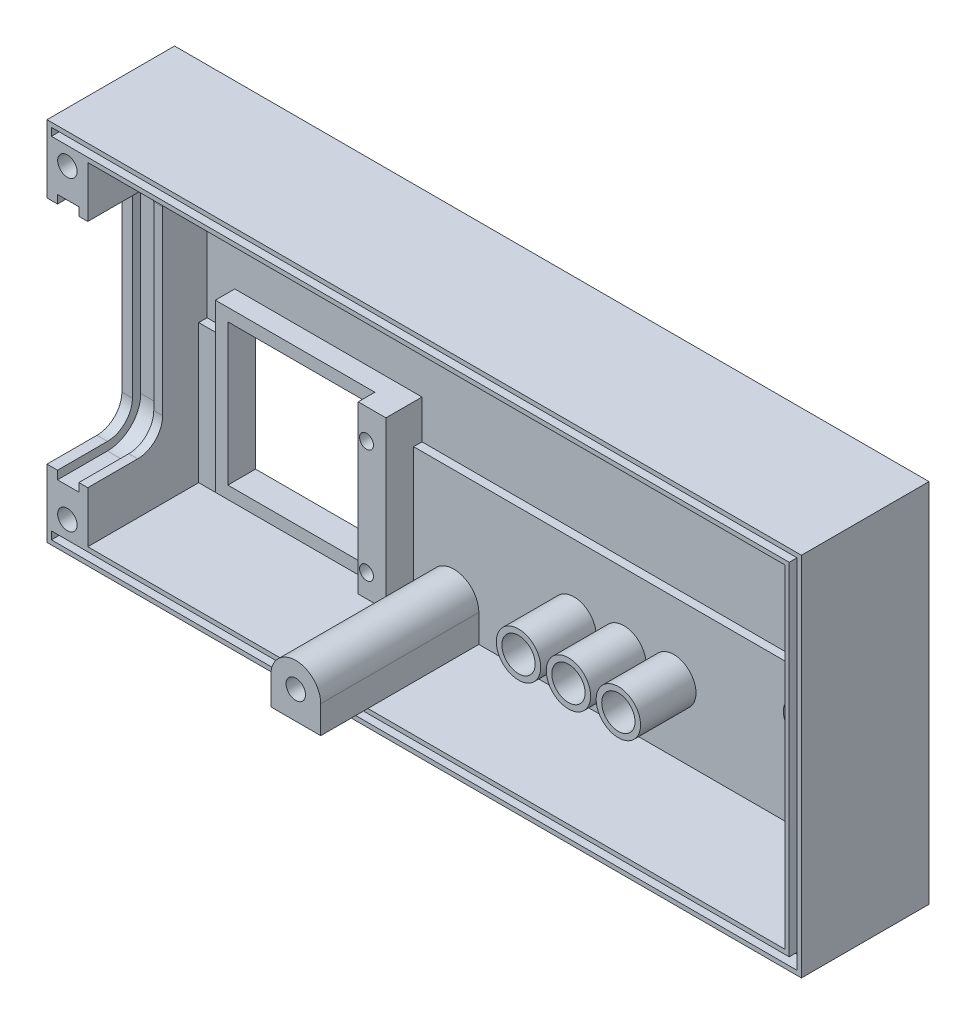
SolidWorks part; units mm, degrees
ref_plane "Płaszczyzna przednia" through (0, 0, 0) normal (0, 0, 1) x (1, 0, 0)
ref_plane "Płaszczyzna górna" through (0, 0, 0) normal (0, 1, 0) x (1, 0, 0)
ref_plane "Płaszczyzna prawa" through (0, 0, 0) normal (1, 0, 0) x (0, 0, -1)
sketch "Szkic1" plane through (0, 0, 0) normal (0, 0, 1) x (1, 0, 0)
  line L1 (65, -30) -> (-65, -30)
  line L2 (65, -30) -> (65, 30)
  line L3 (65, 30) -> (-65, 30)
  line L4 (-65, -30) -> (-65, 30)
  line L5 (65, -30) -> (-65, 30) construction
  line L6 (65, 30) -> (-65, -30) construction
  point P0 (0, 0)
  dimension "D1" = 130
  dimension "D2" = 60
extrude "Dodanie-wyciągnięcie1" add sketch "Szkic1" along normal blind 20
shell "Skorupa1" thickness 3 removed face at (0, 0, 20) outward yes
sketch "Szkic4" plane through (-65, 0, 0) normal (1, 0, 0) x (0, 0, -1)
  line L4 (0, -30) -> (0, 30)
  line L5 (0, 30) -> (-20, 30)
  line L6 (-20, 30) -> (-20, -30)
  line L7 (-20, -30) -> (0, -30)
  line L8 (0, -30) -> (0, 30)
  line L9 (0, 30) -> (-20, 30)
  line L10 (-20, 30) -> (-20, -30)
  line L11 (-20, -30) -> (0, -30)
  dimension "D1" = 0
extrude "Wytnij-wyciągnięcie1" cut sketch "Szkic4" against normal blind 1.1
sketch "Szkic5" plane through (-66.1, 0, 0) normal (1, 0, 0) x (0, 0, -1)
  line L0 (-20, 30) -> (-20, -30) construction
  line L1 (-20, 22.275) -> (-11, 22.275)
  line L2 (-26, 16.275) -> (-26, -16.275)
  line L3 (-20, -22.275) -> (-11, -22.275)
  line L4 (-5, 16.275) -> (-5, -16.275)
  line L9 (-20, -30) -> (0, -30)
  line L10 (0, -30) -> (0, 30)
  line L11 (0, 30) -> (-20, 30)
  line L12 (-20, 30) -> (-20, -30)
  line L13 (-20, -30) -> (0, -30)
  line L14 (0, -30) -> (0, 30)
  line L15 (0, 30) -> (-20, 30)
  line L16 (-20, 30) -> (-20, -30)
  arc A0 (-5, -16.275) -> (-11, -22.275) centre (-11, -16.275) cw
  arc A1 (-5, 16.275) -> (-11, 22.275) centre (-11, 16.275) ccw
  arc A2 (-20, -22.275) -> (-26, -16.275) centre (-20, -16.275) cw
  arc A3 (-26, 16.275) -> (-20, 22.275) centre (-20, 16.275) cw
  point P8 (-5, 0)
  point P17 (-20, 22.175)
  point P19 (0, 0)
  line M5 (-20, -30) -> (0, -30)
  line M6 (0, -30) -> (0, 30)
  line M7 (0, 30) -> (-20, 30)
  line M8 (-20, 30) -> (-20, -30)
  dimension "D3" = 6
  dimension "D4" = 6
  dimension "D5" = 6
  dimension "D6" = 6
  dimension "D1" = 32.55
  dimension "D2" = 0
  dimension "D7" = 21
extrude "Dodanie-wyciągnięcie2" add sketch "Szkic5" along normal blind 3.85 contours A1 L4 A0 L3 L1 M8 M5 M6 M7 region at (-66.1, 26.1375, 19.3675)
sketch "Szkic7" plane through (-62.25, 0, 0) normal (1, 0, 0) x (0, 0, -1)
  line L0 (-20, 20.775) -> (-11, 20.775)
  line L1 (-6.5, 16.275) -> (-6.5, -16.275)
  line L2 (-11, -20.775) -> (-20, -20.775)
  line L3 (-20, 22.275) -> (-20, 20.775)
  line L4 (-20, -20.775) -> (-20, -22.275)
  line L8 (-5, 16.275) -> (-5, -16.275)
  line L9 (-11, -22.275) -> (-20, -22.275)
  line L15 (-20, -22.275) -> (-20, -30)
  line L24 (-20, -30) -> (0, -30)
  line L25 (0, -30) -> (0, 30)
  line L26 (0, 30) -> (-20, 30)
  line L27 (-20, 30) -> (-20, 22.275)
  line L28 (-20, 22.275) -> (-11, 22.275)
  line L29 (-5, 16.275) -> (-5, -16.275)
  line L30 (-11, -22.275) -> (-20, -22.275)
  line L31 (-20, -22.275) -> (-20, -30)
  line L32 (-20, -30) -> (0, -30)
  line L33 (0, -30) -> (0, 30)
  line L34 (0, 30) -> (-20, 30)
  line L35 (-20, 30) -> (-20, 22.275)
  line L36 (-20, 22.275) -> (-11, 22.275)
  arc A0 (-6.5, 16.275) -> (-11, 20.775) centre (-11, 16.275) ccw
  arc A1 (-11, -20.775) -> (-6.5, -16.275) centre (-11, -16.275) ccw
  arc A6 (-5, 16.275) -> (-11, 22.275) centre (-11, 16.275) ccw
  arc A7 (-11, -22.275) -> (-5, -16.275) centre (-11, -16.275) ccw
  arc A8 (-5, 16.275) -> (-11, 22.275) centre (-11, 16.275) ccw
  arc A9 (-11, -22.275) -> (-5, -16.275) centre (-11, -16.275) ccw
  arc M11 (-11, 22.275) -> (-5, 16.275) centre (-11, 16.275) cw
  line M12 (-5, 16.275) -> (-5, -16.275)
  arc M13 (-5, -16.275) -> (-11, -22.275) centre (-11, -16.275) cw
  line M14 (-11, -22.275) -> (-20, -22.275)
  line M15 (-20, -22.275) -> (-20, -30)
  line M16 (-20, -30) -> (0, -30)
  line M17 (0, -30) -> (0, 30)
  line M18 (0, 30) -> (-20, 30)
  line M19 (-20, 30) -> (-20, 22.275)
  line M20 (-20, 22.275) -> (-11, 22.275)
  dimension "D1" = 0
  dimension "D2" = 1.5
extrude "Dodanie-wyciągnięcie3" add sketch "Szkic7" along normal blind 1.6 contours M20 M11 M12 M13 M14 M15 M16 M17 M18 M19 | M20 M14 M13 M12 M11 region at (-62.25, 21.525, 19.5299) region at (-62.25, 26.1375, 19.3675)
sketch "Szkic8" plane through (-66.1, 0, 0) normal (1, 0, 0) x (0, 0, -1)
  line L0 (-11, -20.775) -> (-20, -20.775) construction
  line L1 (-6.5, 16.275) -> (-6.5, -16.275) construction
  line L2 (-20, 20.775) -> (-11, 20.775) construction
  line L3 (-11, -20.775) -> (-20, -20.775)
  line L4 (-6.5, 16.275) -> (-6.5, -16.275)
  line L5 (-20, 20.775) -> (-11, 20.775)
  line L9 (-20, 20.775) -> (-20, -20.775)
  line L11 (-20, 20.975) -> (-11, 20.975)
  line L12 (-6.3, 16.275) -> (-6.3, -16.275)
  line L13 (-11, -20.975) -> (-20, -20.975)
  line L14 (-20, 20.775) -> (-20, 20.975)
  line L15 (-20, -20.775) -> (-20, -20.975)
  arc A0 (-11, -20.775) -> (-6.5, -16.275) centre (-11, -16.275) ccw construction
  arc A1 (-6.5, 16.275) -> (-11, 20.775) centre (-11, 16.275) ccw construction
  arc A2 (-11, -20.775) -> (-6.5, -16.275) centre (-11, -16.275) ccw
  arc A3 (-6.5, 16.275) -> (-11, 20.775) centre (-11, 16.275) ccw
  arc A6 (-6.3, 16.275) -> (-11, 20.975) centre (-11, 16.275) ccw
  arc A7 (-11, -20.975) -> (-6.3, -16.275) centre (-11, -16.275) ccw
  line M10 (-20, 22.275) -> (-20, -22.275)
  dimension "D2" = 0.2
  dimension "D1" = 41.55
  dimension "D3" = 41.95
extrude "Wytnij-wyciągnięcie2" cut sketch "Szkic8" against normal through all contours M10 region at (-66.1, 0, 13.3404)
sketch "Szkic9" plane through (0, 0, 20) normal (0, 0, 1) x (1, 0, 0)
  line L0 (-68, 33) -> (-68, 20.775) construction
  line L1 (68, 33) -> (-68, 33) construction
  line L4 (-19.15, -25) -> (-19.15, -30)
  line L9 (-60.65, -30) -> (65, -30) construction
  line L10 (-19.15, -30) -> (-10.15, -30)
  line L11 (-10.15, -30) -> (-10.15, -25) construction
  line L12 (-10.15, -30) -> (-10.15, -25)
  line L13 (-60.65, -20.775) -> (-60.65, -30) construction
  circle A2 centre (-64.325, 27.5875) radius 1.75
  circle A3 centre (-64.325, -27.5875) radius 1.75
  circle A4 centre (-14.65, -25) radius 1.75
  arc A5 (-10.15, -25) -> (-19.15, -25) centre (-14.65, -25) ccw
  point P0 (-64.325, 27.5875)
  point P3 (-64.325, -27.5875)
  line M16 (-60.65, 30) -> (65, 30)
  line M18 (65, -30) -> (-60.65, -30)
  dimension "D8" = 3.5
  dimension "D9" = 3.5
  dimension "D11" = 3.5
  dimension "D12" = 4.5
  dimension "D1" = 3.675
  dimension "D2" = 5.4125
  dimension "D10" = 46
  dimension "D13" = 5
  dimension "D3" = 2
extrude "Dodanie-wyciągnięcie4" add sketch "Szkic9" along direction (0, 0, 1) on the side against the normal up to surface (20 mm away) and the other way blind 8.5 contours M16 | L12 A5 L4 A4 M18 region at (-14.65, -20.6309, 20) up to face at (2.175, 0, 0)
extrude "Wytnij-wyciągnięcie3" cut sketch "Szkic9<3>" against normal through all contours A2 | A3 | A4 region at (-64.325, 27.5875, 20)
sketch "Szkic9<3>" plane through (0, 0, 20) normal (0, 0, 1) x (1, 0, 0) same geometry as "Szkic9"
sketch "Szkic10" plane through (0, 0, -3) normal (0, 0, -1) x (-1, 0, 0)
  circle A1 centre (64.325, 27.5875) radius 3
  circle A2 centre (64.325, -27.5875) radius 3
  circle A3 centre (14.65, -25) radius 3
  circle M11 centre (14.65, -25) radius 1.75
  dimension "D1" = 6
  dimension "D2" = 6
  dimension "D3" = 6
extrude "Wytnij-wyciągnięcie4" cut sketch "Szkic10" against normal offset from surface (11 mm away) 12 contours A2 | A1 up to face at (-62.575, 27.5875, 20)
sketch "Szkic11" plane through (0, 0, 20) normal (0, 0, 1) x (1, 0, 0)
  line L22 (-10.15, -30.8) -> (-19.15, -30.8)
  line L23 (-19.15, -30.8) -> (-10.15, -30.8)
  line L24 (-61.45, -30.8) -> (-67.2, -30.8)
  line L25 (-61.45, 30.8) -> (-67.2, 30.8)
  line L26 (-67.2, 30.8) -> (-67.2, 32.2)
  line L27 (-67.2, -32.2) -> (-67.2, -30.8)
  line L28 (-10.15, -30.8) -> (-19.15, -30.8)
  line L29 (-66.9, -23.075) -> (-66.9, -21.575)
  line L31 (-66.9, -21.575) -> (-67.2, -21.575)
  line L32 (-66.9, -21.575) -> (-67.2, -21.575)
  line L33 (-67.2, 21.575) -> (-66.9, 21.575)
  line L34 (-67.2, 21.575) -> (-66.9, 21.575)
  line L35 (-66.9, 21.575) -> (-66.9, 23.075)
  line L46 (-67.2, -21.575) -> (-67.2, -32.2)
  line L47 (-67.2, -32.2) -> (67.2, -32.2)
  line L48 (67.2, -32.2) -> (67.2, 32.2)
  line L49 (67.2, 32.2) -> (-67.2, 32.2)
  line L50 (-67.2, 32.2) -> (-67.2, 21.575)
  line L51 (-66.9, 23.075) -> (-61.45, 23.075)
  line L52 (-61.45, 23.075) -> (-61.45, 30.8)
  line L53 (-61.45, 30.8) -> (65.8, 30.8)
  line L54 (65.8, 30.8) -> (65.8, -30.8)
  line L55 (65.8, -30.8) -> (-10.15, -30.8)
  line L58 (-19.15, -30.8) -> (-61.45, -30.8)
  line L59 (-61.45, -30.8) -> (-61.45, -23.075)
  line L60 (-61.45, -23.075) -> (-66.9, -23.075)
  line L62 (-67.2, -32.2) -> (67.2, -32.2)
  line L63 (67.2, -32.2) -> (67.2, 32.2)
  line L64 (67.2, 32.2) -> (-67.2, 32.2)
  line L68 (-61.45, 30.8) -> (65.8, 30.8)
  line L69 (65.8, 30.8) -> (65.8, -30.8)
  line L70 (65.8, -30.8) -> (-10.15, -30.8)
  line L73 (-19.15, -30.8) -> (-61.45, -30.8)
  dimension "D1" = 0.8
extrude "Wytnij-wyciągnięcie5" cut sketch "Szkic11" against normal blind 2.5 contours L23 L73 L24 L27 L62 L63 L64 L26 L25 L68 L69 L70 region at (27.825, -30.949, 20)
sketch "Szkic12" plane through (0, 0, -3) normal (0, 0, -1) x (-1, 0, 0)
  line L0 (-25, 33) -> (-25, -18) construction
  line L1 (-68, -33) -> (-48, -33) construction
  line L2 (-68, -33) -> (-68, -13) construction
  line L3 (-68, -13) -> (-48, -13) construction
  line L4 (-48, -33) -> (-48, -13) construction
  line L5 (-68, 33) -> (68, 33) construction
  line L6 (-25, -18) -> (-68, -18) construction
  circle A0 centre (-48, -13) radius 3.25
  circle A1 centre (-25, -18) radius 3
  circle A2 centre (-16, -18) radius 3
  circle A3 centre (-7, -18) radius 3
  dimension "D1" = 6.5
  dimension "D6" = 6
  dimension "D2" = 20
  dimension "D3" = 20
  dimension "D4" = 51
  dimension "D5" = 43
  dimension "D7" = 3
extrude "Wytnij-wyciągnięcie6" cut sketch "Szkic12" against normal up to next
extrude "Wytnij-wyciągnięcie7" cut sketch "Szkic10<4>" against normal offset from surface (19.5 mm away) 12 contours A3 M11 region at (-11.7349, -25, -3) up to face at (-12.9, -25, 28.5)
sketch "Szkic10<4>" plane through (0, 0, -3) normal (0, 0, -1) x (-1, 0, 0) same geometry as "Szkic10"
sketch "Szkic13" plane through (0, 0, 0) normal (0, 0, 1) x (1, 0, 0)
  circle A0 centre (7, -18) radius 3 construction
  circle A1 centre (16, -18) radius 3 construction
  circle A2 centre (25, -18) radius 3 construction
  circle A3 centre (7, -18) radius 3
  circle A4 centre (16, -18) radius 3
  circle A5 centre (25, -18) radius 3
  circle A6 centre (7, -18) radius 4
  circle A7 centre (16, -18) radius 4
  circle A8 centre (25, -18) radius 4
  dimension "D1" = 8
  dimension "D2" = 8
  dimension "D3" = 8
extrude "Dodanie-wyciągnięcie5" add sketch "Szkic13" along normal blind 10
sketch "Szkic14" plane through (0, 0, 0) normal (0, 0, 1) x (1, 0, 0)
  line L0 (65, -30) -> (65, 30) construction
  line L1 (65, -5) -> (-60.65, -5)
  line L2 (65, -5) -> (65, 30)
  line L3 (65, 30) -> (-60.65, 30)
  line L6 (-60.65, -30) -> (-60.65, 30) construction
  line L7 (-60.65, -30) -> (-60.65, 30)
  point P8 (0, 0)
  point P11 (-60.65, -4.997)
  point P12 (0, 0)
  point P13 (-60.6941, 30)
  line M7 (65, -30) -> (65, 30)
  line M8 (65, 30) -> (-60.65, 30)
  line M9 (-60.65, 30) -> (-60.65, -30)
  dimension "D2" = 35
extrude "Wytnij-wyciągnięcie8" cut sketch "Szkic14" against normal blind 1.5 contours L1 M7 M8 M9 region at (2.175, 12.5, 0)
sketch "Szkic17" plane through (0, 0, -1.5) normal (0, 0, 1) x (1, 0, 0)
  line L1 (-53.4, -0.25) -> (-27.9, -0.25)
  line L2 (-53.4, -0.25) -> (-53.4, -25.75)
  line L3 (-53.4, -25.75) -> (-27.9, -25.75)
  line L4 (-27.9, -0.25) -> (-27.9, -25.75)
  line L5 (-60.65, -30) -> (-19.15, -30) construction
  line L6 (-60.65, -30) -> (-60.65, -5) construction
  line L7 (-25.65, -28) -> (-55.65, -28)
  line L8 (-25.65, -28) -> (-25.65, 2)
  line L9 (-25.65, 2) -> (-55.65, 2)
  line L10 (-55.65, -28) -> (-55.65, 2)
  point P12 (-40.65, -25.75)
  point P13 (-40.65, -28)
  point P14 (-53.4, -13)
  point P15 (-55.65, -13)
  dimension "D1" = 25.5
  dimension "D2" = 25.5
  dimension "D3" = 5
  dimension "D4" = 2
  dimension "D5" = 30
  dimension "D6" = 30
extrude "Dodanie-wyciągnięcie6" add sketch "Szkic17" along normal blind 3.5
sketch "Szkic19" plane through (0, 0, 0) normal (0, 0, 1) x (1, 0, 0)
  line L0 (-53.4, -0.25) -> (-53.4, -25.75) construction
  line L1 (-27.9, -0.25) -> (-53.4, -0.25) construction
  line L2 (-27.9, -25.75) -> (-27.9, -0.25) construction
  line L3 (-53.4, -25.75) -> (-27.9, -25.75) construction
  line L4 (-53.4, -0.25) -> (-53.4, -25.75)
  line L5 (-27.9, -0.25) -> (-53.4, -0.25)
  line L6 (-27.9, -25.75) -> (-27.9, -0.25)
  line L7 (-53.4, -25.75) -> (-27.9, -25.75)
extrude "Wytnij-wyciągnięcie10" cut sketch "Szkic19" against normal through all
sketch "Szkic20" plane through (0, 0, -1.5) normal (0, 0, 1) x (1, 0, 0)
  line L0 (-55.65, -28) -> (-25.65, -28) construction
  line L1 (-26.9, -28) -> (-21.9, -28)
  line L2 (-26.9, -28) -> (-26.9, 2)
  line L3 (-26.9, 2) -> (-21.9, 2)
  line L4 (-21.9, -28) -> (-21.9, 2)
  line L5 (-27.9, -25.75) -> (-27.9, -0.25) construction
  dimension "D1" = 1
  dimension "D2" = 5
  dimension "D3" = 30
extrude "Dodanie-wyciągnięcie7" add sketch "Szkic20" along normal offset from surface (6.5 mm away) 3 up to face at (-40.65, -13, 2) offset beyond the face yes
sketch "Szkic22" plane through (0, 0, 5) normal (0, 0, 1) x (1, 0, 0)
  line L1 (-53.4, -25.75) -> (-27.9, -25.75) construction
  line L3 (-26.9, 2) -> (-26.9, -28) construction
  circle A0 centre (-25.4, -23.9) radius 1.25
  circle A1 centre (-25.4, -3.4) radius 1.25
  dimension "D3" = 2.5
  dimension "D4" = 2.5
  dimension "D5" = 1.5
  dimension "D1" = 1.85
  dimension "D2" = 20.5
  dimension "D6" = 1.5
extrude "Wytnij-wyciągnięcie11" cut sketch "Szkic22" against normal offset from surface (7 mm away) 1 up to face at (-40.65, -13, -3)
